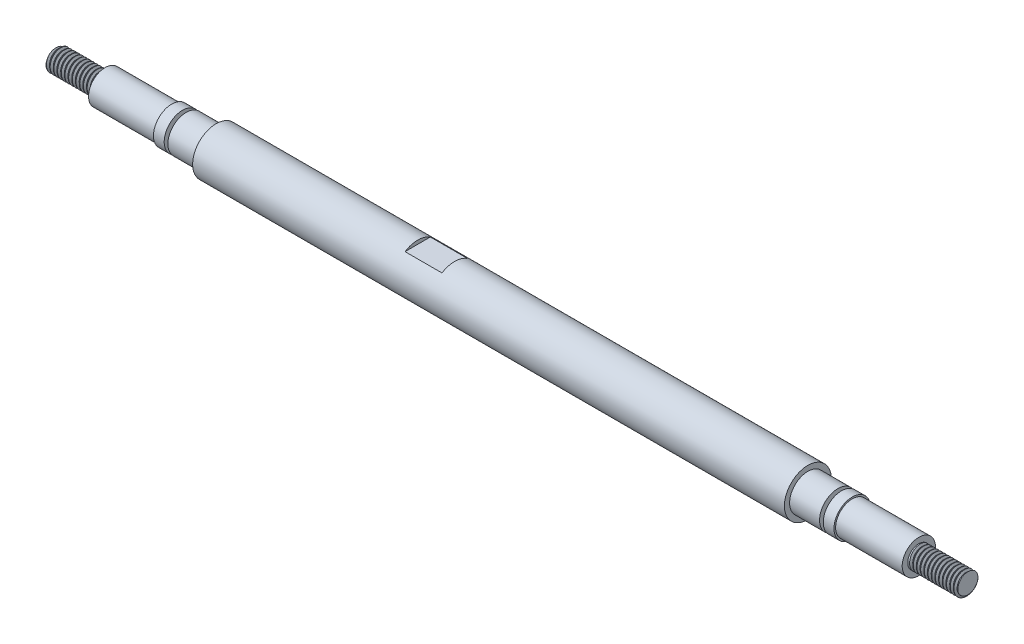
SolidWorks part; units mm, degrees
material "1060-H12 Rod (SS)"
ref_plane "Front Plane" through (0, 0, 0) normal (0, 0, 1) x (1, 0, 0)
ref_plane "Top Plane" through (0, 0, 0) normal (0, 1, 0) x (1, 0, 0)
ref_plane "Right Plane" through (0, 0, 0) normal (1, 0, 0) x (0, 0, -1)
sketch "Sketch1" plane through (0, 0, 0) normal (0, 0, 1) x (1, 0, 0)
  line L0 (0, 0) -> (0, 3)
  line L1 (0, 3) -> (13, 3)
  line L2 (13, 3) -> (13, 4.5)
  line L3 (13, 4.5) -> (31, 4.5)
  line L4 (31, 4.5) -> (31, 4.945)
  line L5 (31, 4.945) -> (33.9, 4.945)
  line L6 (33.9, 4.945) -> (33.9, 3.445)
  line L7 (33.9, 3.445) -> (34.9, 3.445)
  line L8 (34.9, 3.445) -> (34.9, 4.945)
  line L9 (34.9, 4.945) -> (43, 4.945)
  line L10 (43, 4.945) -> (43, 6.35)
  line L11 (43, 6.35) -> (203, 6.35)
  line L12 (203, 6.35) -> (203, 4.945)
  line L13 (203, 4.945) -> (211.1, 4.945)
  line L14 (211.1, 4.945) -> (211.1, 3.445)
  line L15 (211.1, 3.445) -> (212.1, 3.445)
  line L16 (212.1, 3.445) -> (212.1, 4.945)
  line L17 (212.1, 4.945) -> (215, 4.945)
  line L18 (215, 4.945) -> (215, 4.5)
  line L19 (215, 4.5) -> (233, 4.5)
  line L20 (233, 4.5) -> (233, 3)
  line L21 (233, 3) -> (246, 3)
  line L22 (246, 3) -> (246, 0)
  line L23 (246, 0) -> (0, 0)
  line L24 (123, 0) -> (123, 73.795) construction
  point P26 (123, 0)
  dimension "D1" = 246
  dimension "D2" = 220
  dimension "D3" = 184
  dimension "D4" = 176.2
  dimension "D5" = 160
  dimension "D6" = 1.5
  dimension "D7" = 1
  dimension "D8" = 3
  dimension "D9" = 4.5
  dimension "D10" = 4.945
  dimension "D11" = 6.35
revolve "Revolve1" add sketch "Sketch1" angle 360 about L23
sketch "Sketch3" plane through (0, 0, 0) normal (0, 0, 1) x (1, 0, 0)
  line L1 (97.5, 5.35) -> (107.5, 5.35)
  line L2 (97.5, 5.35) -> (97.5, 6.35)
  line L3 (97.5, 6.35) -> (107.5, 6.35)
  line L4 (107.5, 5.35) -> (107.5, 6.35)
  dimension "D1" = 97.5
  dimension "D2" = 5.35
  dimension "D3" = 1
  dimension "D4" = 10
extrude "Cut-Extrude1" cut sketch "Sketch3" against normal mid plane 10
thread "Thread3" pitch 1 method cut profile "Thread Profile3" start angle 0, offset 0, length 0, pitch 1, diameter 6
ref_plane "Plane3" through (233, 0, -3) normal (0, -1, 0) x (0, 0, -1)
sketch "Thread Profile3" plane through (233, 0, -3) normal (0, -1, 0) x (0, 0, -1)
  line L0 (0, 0) -> (0, 1) construction
  line L11 (0, 0) -> (0, 0.875)
  line L12 (0, 0.875) -> (-0.5413, 0.5625)
  line L13 (-0.5413, 0.5625) -> (-0.5413, 0.3125)
  line L15 (-0.5413, 0.3125) -> (0, 0)
  line L17 (-0.5413, 0.4375) -> (0, 0.4375) construction
  point P2 (0, 0)
  dimension "Pitch" = 1
  dimension "Profile_Angle" = 60
  dimension "Profile_Land" = 0.25
  dimension "Profile_Height" = 0.5413
thread "Thread4" pitch 1 method cut profile "Thread Profile4" start angle 0, offset 0, length 0, pitch 1, diameter 6
ref_plane "Plane4" through (13, 0, 3) normal (0, -1, 0) x (0, 0, 1)
sketch "Thread Profile4" plane through (13, 0, 3) normal (0, -1, 0) x (0, 0, 1)
  line L0 (0, 0) -> (0, 1) construction
  line L11 (0, 0) -> (0, 0.875)
  line L12 (0, 0.875) -> (-0.5413, 0.5625)
  line L13 (-0.5413, 0.5625) -> (-0.5413, 0.3125)
  line L15 (-0.5413, 0.3125) -> (0, 0)
  line L17 (-0.5413, 0.4375) -> (0, 0.4375) construction
  point P2 (0, 0)
  dimension "Pitch" = 1
  dimension "Profile_Angle" = 60
  dimension "Profile_Land" = 0.25
  dimension "Profile_Height" = 0.5413
